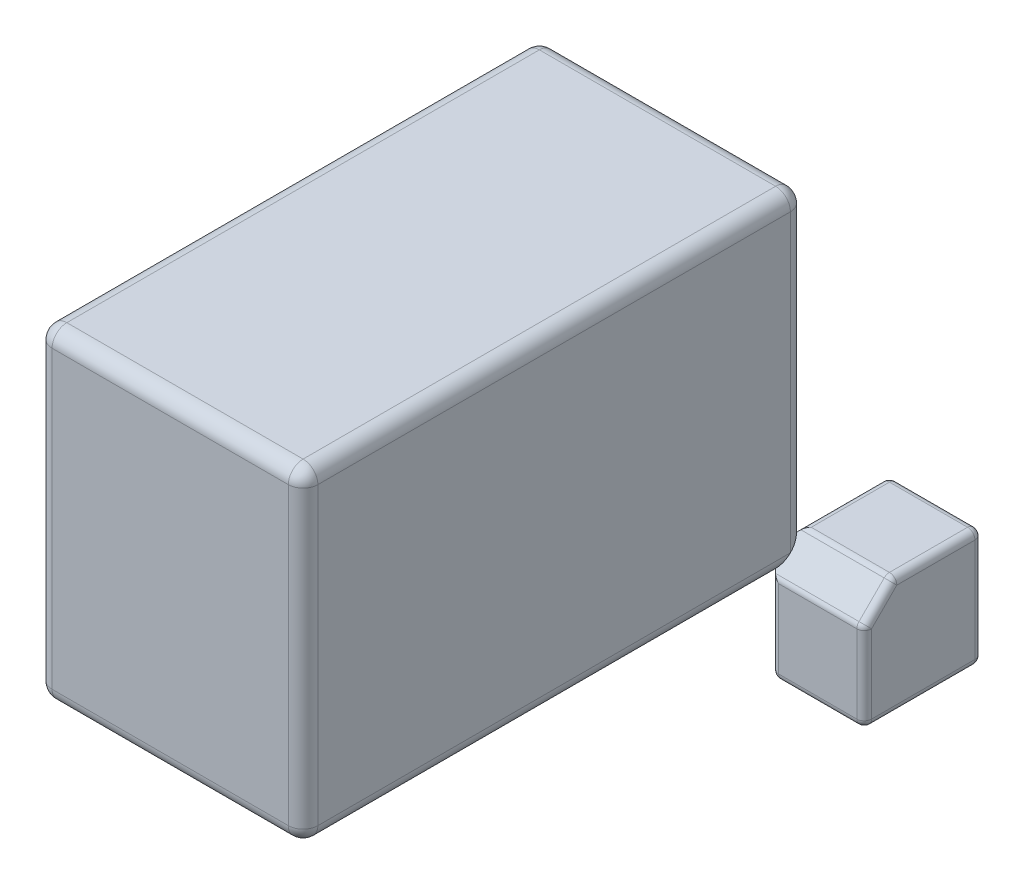
SolidWorks part; units mm, degrees
ref_plane "Front Plane" through (0, 0, 0) normal (0, 0, 1) x (1, 0, 0)
ref_plane "Top Plane" through (0, 0, 0) normal (0, 1, 0) x (1, 0, 0)
ref_plane "Right Plane" through (0, 0, 0) normal (1, 0, 0) x (0, 0, -1)
sketch "Sketch1" plane through (0, 0, 0) normal (0, 0, 1) x (1, 0, 0)
  line L1 (0, 0) -> (18, 0)
  line L2 (0, 0) -> (0, 22)
  line L3 (0, 22) -> (18, 22)
  line L4 (18, 0) -> (18, 22)
  dimension "D1" = 18
  dimension "D2" = 22
extrude "Boss-Extrude1" add sketch "Sketch1" along normal blind 34
sketch "Sketch2" plane through (0, 0, 0) normal (0, 0, -1) x (-1, 0, 0)
  line L0 (-18, 0) -> (-18, 22) construction
  line L1 (-16, 2) -> (-24, 2)
  line L2 (-16, 2) -> (-16, -6)
  line L3 (-16, -6) -> (-24, -6)
  line L4 (-24, 2) -> (-24, -6)
  line L5 (0, 0) -> (-18, 0) construction
  dimension "D1" = 2
  dimension "D2" = 2
  dimension "D3" = 8
  dimension "D4" = 8
shell "Shell1" thickness 1
extrude "Boss-Extrude3" add sketch "Sketch2" along normal blind 6 and the other way blind 2 contours L3 L4 L1 L2
chamfer "Chamfer2" distance 2 angle 45 3 edges at (21, 2, 2) (16, 2, -3) (16, -3, 2)
fillet "Fillet1" radius 1 12 edges at (0, 11, 0) (8, 0, 0) (18, 12, 0) (9, 22, 0) (9, 0, 34) (18, 11, 34) (9, 22, 34) (0, 22, 17) (18, 22, 17) (18, 0, 18) (0, 0, 17) (0, 11, 34)
fillet "Fillet2" radius 0.5 18 edges at (24, -6, -2) (20, -6, -6) (17, -6, 1) (21, -6, 2) (16, -6, -3) (16, -3, -6) (16, 0, -3) (16, -3, 0) (21, 0, 2) (17, 1, -6) (21, 2, -6) (24, 2, -3) (21, 2, 0) (18, 2, -3) (24, -3, 2) (24, -2, -6) (18, -3, 2) (24, 1, 1)
